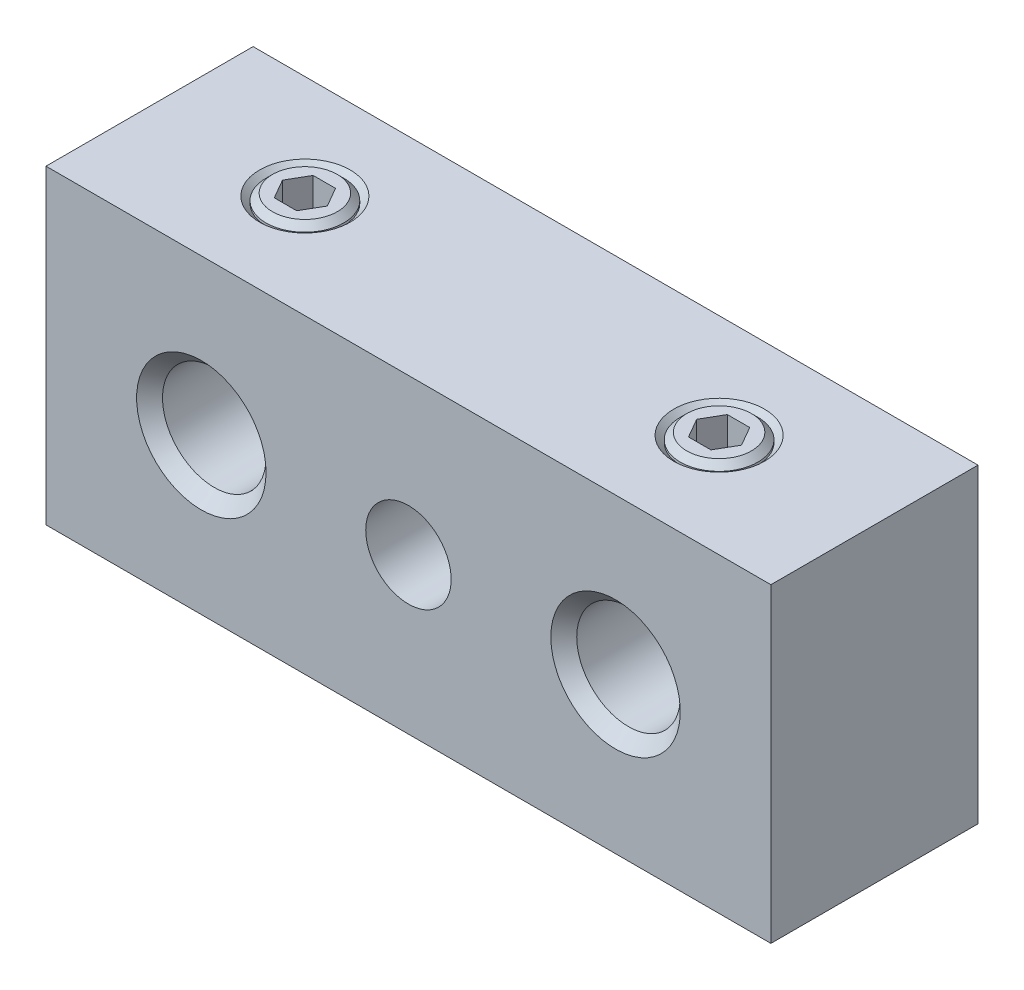
SolidWorks part; units mm, degrees
material "1060 Alloy"
material "Plain Carbon Steel"
material "1060 Alloy"
ref_plane "Front Plane" through (0, 0, 0) normal (0, 0, 1) x (1, 0, 0)
ref_plane "Top Plane" through (0, 0, 0) normal (0, 1, 0) x (1, 0, 0)
ref_plane "Right Plane" through (0, 0, 0) normal (1, 0, 0) x (0, 0, -1)
sketch "Sketch1" plane through (0, 0, 0) normal (0, 0, 1) x (1, 0, 0)
  line L0 (0, 80.0881) -> (0, -86.0205) construction
  line L1 (84.3358, 0) -> (-30.3718, 0) construction
  line L2 (0, -6) -> (14, -6)
  line L3 (0, -6) -> (0, 6)
  line L4 (0, 6) -> (14, 6)
  line L5 (14, -6) -> (14, 6)
  dimension "D1" = 12
  dimension "D2" = 28
extrude "Boss-Extrude1" add sketch "Sketch1" along normal mid plane 8
sketch "Sketch2" plane through (0, 0, 0) normal (0, 0, 1) x (1, 0, 0)
  line L0 (0, 17.5467) -> (0, -15.8034) construction
  line L1 (-16.9143, 0) -> (36.7285, 0) construction
  circle A0 centre (8, 0) radius 2
  dimension "D2" = 4
  dimension "D1" = 16
extrude "Cut-Extrude1" cut sketch "Sketch2" against normal through all and the other way through all
sketch "Sketch3" plane through (0, 0, 4) normal (0, 0, 1) x (1, 0, 0)
  line L0 (0, 6) -> (0, -6) construction
  circle A0 centre (0, 0) radius 1.65
  dimension "D1" = 3.3
extrude "Cut-Extrude2" cut sketch "Sketch3" against normal through all
cosmetic thread "Cosmetic Thread1"
sketch "Sketch4" plane through (0, 0, 0) normal (0, 1, 0) x (1, 0, 0)
  line L0 (-11.5584, 0) -> (22.8514, 0) construction
  line L1 (0, 10.2523) -> (0, -11.6553) construction
  circle A0 centre (8, 0) radius 1.25
  dimension "D2" = 2.5
  dimension "D1" = 16
extrude "Cut-Extrude3" cut sketch "Sketch4" along normal through all
ref_plane "Plane1" through (0, 1.5, 0) normal (0, 1, 0) x (1, 0, 0)
sketch "Sketch5" plane through (0, 1.5, 0) normal (0, 1, 0) x (1, 0, 0)
  circle A0 centre (8, 0) radius 1.5
  dimension "D1" = 3
extrude "Boss-Extrude2" add sketch "Sketch5" along normal blind 4.6 separate body
chamfer "Chamfer1" distance 0.25 angle 45 1 edges at (8, 6.1, 1.5)
chamfer "Chamfer2" distance 0.5 angle 45 3 edges at (10, 0, -4) (10, 0, 4) (8, 6, 1.25)
sketch "Sketch6" plane through (0, 6.1, 0) normal (0, 1, 0) x (1, 0, 0)
  line L1 (7.134, 0) -> (7.567, -0.75)
  line L2 (7.567, -0.75) -> (8.433, -0.75)
  line L3 (8.433, -0.75) -> (8.866, 0)
  line L4 (8.866, 0) -> (8.433, 0.75)
  line L5 (8.433, 0.75) -> (7.567, 0.75)
  line L6 (7.567, 0.75) -> (7.134, 0)
  circle A0 centre (8, 0) radius 0.75 construction
  dimension "D1" = 1.5
extrude "Cut-Extrude4" cut sketch "Sketch6" against normal blind 2
mirror "Mirror1" about plane through (0, 0, 0) normal (1, 0, 0) of bodies 104 106
combine bodies "Combine1" operation type add bodies to combine 107 104
